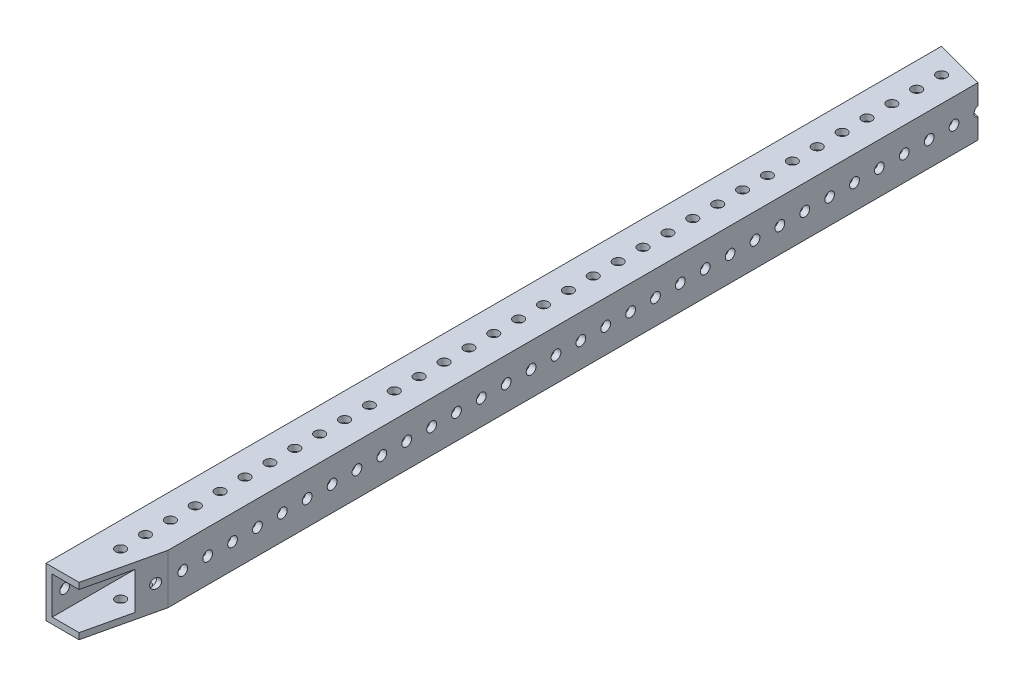
SolidWorks part; units mm, degrees
material "6061-T6 (SS)"
ref_plane "Front Plane" through (0, 0, 0) normal (0, 0, 1) x (1, 0, 0)
ref_plane "Top Plane" through (0, 0, 0) normal (0, 1, 0) x (1, 0, 0)
ref_plane "Right Plane" through (0, 0, 0) normal (1, 0, 0) x (0, 0, -1)
sketch "Sketch1" plane through (0, 0, 0) normal (0, 0, 1) x (1, 0, 0)
  line L0 (-9.525, 9.525) -> (9.525, 9.525)
  line L1 (-12.7, 12.7) -> (12.7, 12.7)
  line L2 (-12.7, 12.7) -> (-12.7, -12.7)
  line L3 (-12.7, -12.7) -> (12.7, -12.7)
  line L4 (12.7, 12.7) -> (12.7, -12.7)
  line L5 (9.525, 9.525) -> (9.525, -9.525)
  line L6 (-9.525, -9.525) -> (9.525, -9.525)
  line L7 (-9.525, 9.525) -> (-9.525, -9.525)
  line L8 (-12.7, 12.7) -> (12.7, -12.7) construction
  line L9 (12.7, 12.7) -> (-12.7, -12.7) construction
  point P5 (0, 0)
  dimension "D1" = 25.4
  dimension "D2" = 25.4
  dimension "D3" = 3.175
extrude "Boss-Extrude1" add sketch "Sketch1" along normal mid plane 457.2
sketch "Sketch2" plane through (0, 12.7, 0) normal (0, 1, 0) x (1, 0, 0)
  circle A2 centre (0, -292.1) radius 2.5527 construction
  circle A3 centre (0, -279.4) radius 2.5527 construction
  circle A6 centre (0, -266.7) radius 2.5527
  circle A9 centre (0, -254) radius 2.5527
  circle A12 centre (0, -241.3) radius 2.5527
  circle A15 centre (0, -228.6) radius 2.5527 construction
  circle A18 centre (0, -215.9) radius 2.5527 construction
  circle A21 centre (0, -203.2) radius 2.5527
  circle A24 centre (0, -190.5) radius 2.5527
  circle A27 centre (0, -177.8) radius 2.5527
  circle A30 centre (0, -165.1) radius 2.5527
  circle A33 centre (0, -152.4) radius 2.5527
  circle A36 centre (0, -139.7) radius 2.5527
  circle A39 centre (0, -127) radius 2.5527
  circle A42 centre (0, -114.3) radius 2.5527
  circle A45 centre (0, -101.6) radius 2.5527
  circle A48 centre (0, -88.9) radius 2.5527
  circle A51 centre (0, -76.2) radius 2.5527
  circle A54 centre (0, -63.5) radius 2.5527
  circle A57 centre (0, -50.8) radius 2.5527
  circle A60 centre (0, -38.1) radius 2.5527
  circle A63 centre (0, -25.4) radius 2.5527
  circle A66 centre (0, -12.7) radius 2.5527
  circle A69 centre (0, 0) radius 2.5527
  circle A72 centre (0, 12.7) radius 2.5527
  circle A75 centre (0, 25.4) radius 2.5527
  circle A78 centre (0, 38.1) radius 2.5527
  circle A81 centre (0, 50.8) radius 2.5527
  circle A84 centre (0, 63.5) radius 2.5527
  circle A87 centre (0, 76.2) radius 2.5527
  circle A90 centre (0, 88.9) radius 2.5527
  circle A93 centre (0, 101.6) radius 2.5527
  circle A96 centre (0, 114.3) radius 2.5527
  circle A99 centre (0, 127) radius 2.5527
  circle A108 centre (0, 152.4) radius 2.5527 [skipped]
  circle A111 centre (0, 139.7) radius 2.5527 [skipped]
  circle A116 centre (0, 139.7) radius 2.5527
  circle A119 centre (0, 152.4) radius 2.5527
  circle A122 centre (0, 165.1) radius 2.5527
  circle A125 centre (0, 177.8) radius 2.5527
  circle A128 centre (0, 190.5) radius 2.5527
  circle A131 centre (0, 203.2) radius 2.5527
  circle A134 centre (0, 215.9) radius 2.5527
  circle A137 centre (0, 228.6) radius 2.5527
  circle A140 centre (0, 241.3) radius 2.5527
  circle A143 centre (0, 254) radius 2.5527
  circle A146 centre (0, 266.7) radius 2.5527
  circle A149 centre (0, 279.4) radius 2.5527
  circle A152 centre (0, 292.1) radius 2.5527
  dimension "D6" = 12.7
  dimension "D5" = 36
  dimension "D8" = 14
extrude "Cut-Extrude1" cut sketch "Sketch2" against normal through all
sketch "Sketch4" plane through (12.7, 0, 0) normal (1, 0, 0) x (0, 0, -1)
  line L1 (-228.6, -12.7) -> (-228.6, 12.7) construction
  line L2 (-228.6, -12.7) -> (228.6, -12.7) construction
  circle A2 centre (-222.25, 0) radius 2.4892
  circle A3 centre (-209.55, 0) radius 2.4892
  circle A16 centre (-196.85, 0) radius 2.4892
  circle A17 centre (-184.15, 0) radius 2.4892
  circle A18 centre (-171.45, 0) radius 2.4892
  circle A19 centre (209.55, 0) radius 2.4892
  circle A20 centre (222.25, 0) radius 2.4892
  circle A21 centre (234.95, 0) radius 2.4892
  circle A22 centre (247.65, 0) radius 2.4892
  circle A23 centre (260.35, 0) radius 2.4892
  circle A24 centre (273.05, 0) radius 2.4892
  circle A25 centre (285.75, 0) radius 2.4892
  circle A26 centre (298.45, 0) radius 2.4892
  circle A27 centre (311.15, 0) radius 2.4892
  circle A28 centre (323.85, 0) radius 2.4892
  circle A29 centre (336.55, 0) radius 2.4892
  circle A30 centre (349.25, 0) radius 2.4892
  circle A31 centre (361.95, 0) radius 2.4892
  circle A32 centre (374.65, 0) radius 2.4892
  circle A35 centre (-158.75, 0) radius 2.4892
  circle A36 centre (-146.05, 0) radius 2.4892
  circle A37 centre (-133.35, 0) radius 2.4892
  circle A38 centre (-120.65, 0) radius 2.4892
  circle A39 centre (-107.95, 0) radius 2.4892
  circle A40 centre (-95.25, 0) radius 2.4892
  circle A41 centre (-82.55, 0) radius 2.4892
  circle A42 centre (-69.85, 0) radius 2.4892
  circle A43 centre (-57.15, 0) radius 2.4892
  circle A44 centre (-44.45, 0) radius 2.4892
  circle A45 centre (-31.75, 0) radius 2.4892
  circle A46 centre (-19.05, 0) radius 2.4892
  circle A47 centre (-6.35, 0) radius 2.4892
  circle A48 centre (6.35, 0) radius 2.4892
  circle A49 centre (19.05, 0) radius 2.4892
  circle A50 centre (31.75, 0) radius 2.4892
  circle A51 centre (44.45, 0) radius 2.4892
  circle A52 centre (57.15, 0) radius 2.4892
  circle A53 centre (69.85, 0) radius 2.4892
  circle A54 centre (82.55, 0) radius 2.4892
  circle A55 centre (95.25, 0) radius 2.4892
  circle A56 centre (107.95, 0) radius 2.4892
  circle A57 centre (120.65, 0) radius 2.4892
  circle A58 centre (133.35, 0) radius 2.4892
  circle A59 centre (146.05, 0) radius 2.4892
  circle A60 centre (158.75, 0) radius 2.4892
  circle A61 centre (171.45, 0) radius 2.4892
  circle A62 centre (184.15, 0) radius 2.4892
  circle A63 centre (196.85, 0) radius 2.4892
  dimension "D2" = 4.9784
  dimension "D1" = 6.35
  dimension "D3" = 12.7
  dimension "D4" = 12.7
  dimension "D5" = 34
  dimension "D6" = 10
  dimension "D7" = 6
extrude "Cut-Extrude3" cut sketch "Sketch4" against normal through all
sketch "Sketch6" plane through (0, 12.7, 0) normal (0, 1, 0) x (1, 0, 0)
  line L1 (12.7, -228.6) -> (-12.7, -228.6) construction
  line L4 (4.1819, -228.6) -> (12.7, -191.7042)
  line L5 (12.7, -228.6) -> (12.7, 228.6) construction
  line L6 (12.7, -191.7042) -> (12.7, -228.6)
  line L7 (12.7, -228.6) -> (4.1819, -228.6)
  point P0 (4.1819, -228.6)
  dimension "D2" = 77
sketch "Sketch7" plane through (0, 12.7, 0) normal (0, 1, 0) x (1, 0, 0)
  line L0 (-12.7, 228.6) -> (12.7, 221.7941)
  line L1 (12.7, -228.6) -> (12.7, 228.6) construction
  line L2 (12.7, 221.7941) -> (12.7, 228.6)
  line L3 (12.7, 228.6) -> (-12.7, 228.6)
  dimension "D1" = 15
extrude "Cut-Extrude4" cut sketch "Sketch6" against normal through all
extrude "Cut-Extrude5" cut sketch "Sketch7" against normal through all
